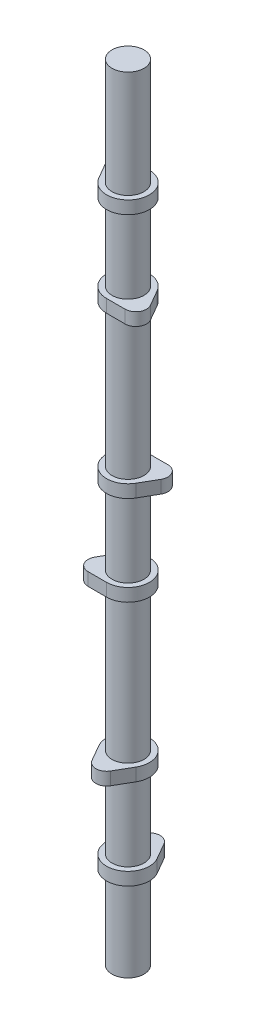
SolidWorks part; units mm, degrees
ref_plane "Front Plane" through (0, 0, 0) normal (0, 0, 1) x (1, 0, 0)
ref_plane "Top Plane" through (0, 0, 0) normal (0, 1, 0) x (1, 0, 0)
ref_plane "Right Plane" through (0, 0, 0) normal (1, 0, 0) x (0, 0, -1)
sketch "Sketch1" plane through (0, 0, 0) normal (0, 1, 0) x (1, 0, 0)
  line L0 (-5.4993, 15.875) -> (-10.9985, 6.35)
  line L1 (5.4993, 15.875) -> (10.9985, 6.35)
  arc A0 (-10.9985, 6.35) -> (10.9985, 6.35) centre (0, 0) ccw
  arc A1 (5.4993, 15.875) -> (-5.4993, 15.875) centre (0, 12.7) ccw
  point P9 (0, 0)
  dimension "D2" = 12.7
  dimension "D3" = 25.4
  dimension "D1" = 12.7
extrude "Boss-Extrude1" add sketch "Sketch1" along normal blind 7.62
ref_axis "Axis1" through (0, 485.438, 0) along (0, -1, 0)
pattern_linear "LPattern1" count 2 spacing 53.34 along (0, 1, 0) of bodies 101
move or copy body "Body-Move/Copy2" bodies to move or copy 102 copy no rotation origin (0, 0, 0) rotation axis (0, 1, 0) rotation angle 180
pattern_linear "LPattern2" count 3 spacing 146.05 along (0, 1, 0) of bodies 101 104
move or copy body "Body-Move/Copy3" bodies to move or copy 107 105 copy no rotation origin (0, 0, 0) rotation axis (0, 1, 0) rotation angle 120
move or copy body "Body-Move/Copy4" bodies to move or copy 108 106 copy no rotation origin (0, 0, 0) rotation axis (0, -1, 0) rotation angle 120
sketch "Sketch2" plane through (0, 0, 0) normal (0, 1, 0) x (1, 0, 0)
  circle A0 centre (0, 0) radius 9.5
  dimension "D1" = 19
extrude "Boss-Extrude2" add sketch "Sketch2" along normal blind 466.09 from offset 49.53 offset against normal yes
